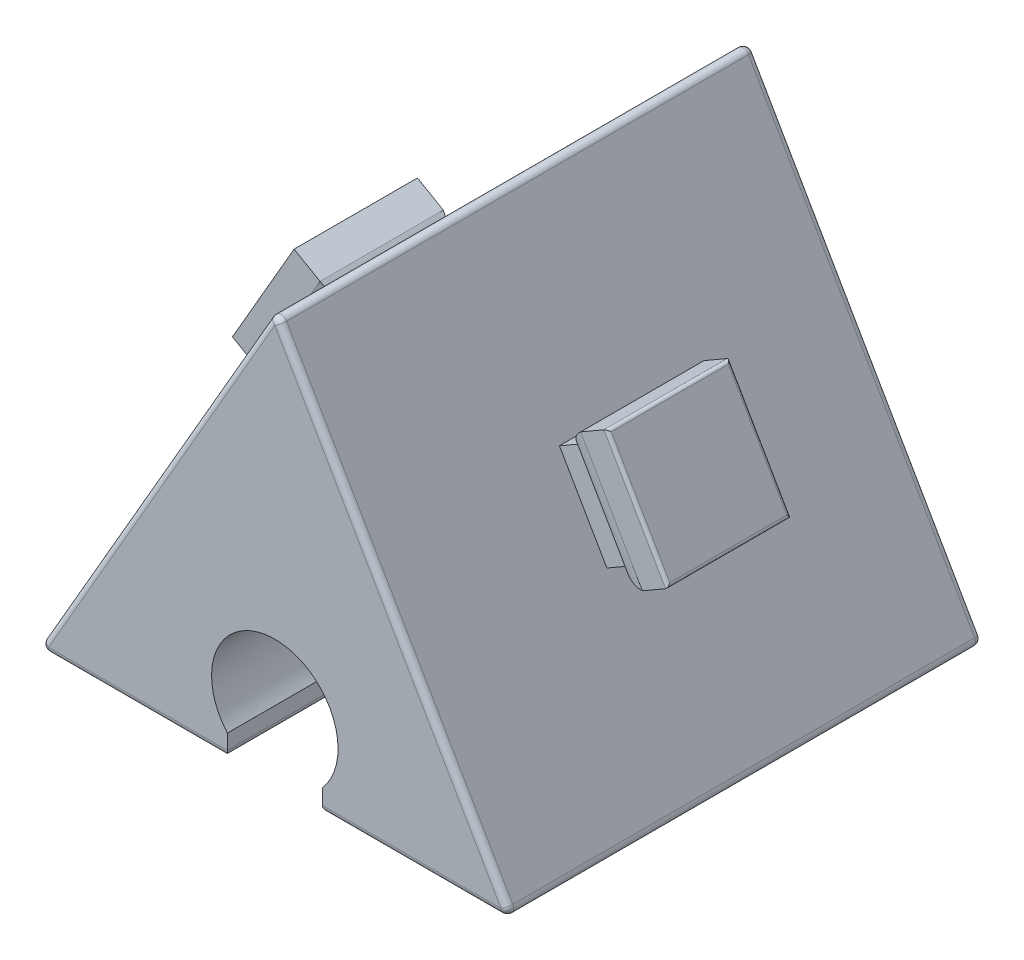
SolidWorks part; units mm, degrees
ref_plane "前视基准面" through (0, 0, 0) normal (0, 0, 1) x (1, 0, 0)
ref_plane "上视基准面" through (0, 0, 0) normal (0, 1, 0) x (1, 0, 0)
ref_plane "右视基准面" through (0, 0, 0) normal (1, 0, 0) x (0, 0, -1)
sketch "草图1" plane through (0, 0, 0) normal (0, 0, 1) x (1, 0, 0)
  line L0 (-7.5, 0) -> (0, 12.9904)
  line L1 (7.5, 0) -> (0, 12.9904)
  line L2 (-7.5, 0) -> (7.5, 0)
extrude "凸台-拉伸1" add sketch "草图1" along normal blind 7.5 and the other way blind 7.5
sketch "草图2" plane through (0, 0, 7.5) normal (0, 0, 1) x (1, 0, 0)
  line L0 (-1.5, 0.6771) -> (-1.5, 0)
  line L1 (-7.5, 0) -> (7.5, 0) construction
  line L3 (1.5, 0.6771) -> (1.5, 0)
  line L4 (1.5, 0) -> (-1.5, 0)
  arc A0 (1.5, 0.6771) -> (-1.5, 0.6771) centre (0, 2) ccw
extrude "切除-拉伸1" cut sketch "草图2" against normal up to next
sketch "草图3" plane through (0, 0, 0) normal (0, 0, 1) x (1, 0, 0)
  line L0 (3.5864, 8.1328) -> (5.0864, 5.5347)
  line L1 (5.9151, 7.7452) -> (6.8901, 6.0564)
  line L2 (0, -1) -> (0, 14) construction
  line L3 (0, -7.1447) -> (0, 7.1447) construction
  line L4 (-4.9401, 9.4339) -> (-4.1222, 8.9617)
  line L5 (-5.9151, 7.7452) -> (-4.9401, 9.4339)
  line L6 (-6.8901, 6.0564) -> (-6.0722, 5.5842)
  line L7 (6.8901, 6.0564) -> (6.0722, 5.5842)
  line L8 (5.9151, 7.7452) -> (4.9401, 9.4339)
  line L9 (4.9401, 9.4339) -> (4.1222, 8.9617)
  line L10 (-5.9151, 7.7452) -> (-6.8901, 6.0564)
  line L11 (-3.5864, 8.1328) -> (-5.0864, 5.5347)
  arc A0 (4.1222, 8.9617) -> (3.5864, 8.1328) centre (5.4821, 7.4952) ccw
  arc A1 (5.0864, 5.5347) -> (6.0722, 5.5842) centre (5.4821, 7.4952) ccw
  arc A2 (-5.0864, 5.5347) -> (-6.0722, 5.5842) centre (-5.4821, 7.4952) cw
  arc A3 (-4.1222, 8.9617) -> (-3.5864, 8.1328) centre (-5.4821, 7.4952) cw
extrude "凸台-拉伸2" add sketch "草图3" along normal blind 2 and the other way blind 2
sketch "草图5" plane through (0, 0, 0) normal (0, 0, 1) x (1, 0, 0)
  line L0 (3.5864, 8.1328) -> (5.0864, 5.5347)
  line L1 (5.0864, 5.5347) -> (4.5, 5.1962)
  line L2 (7.5, 0) -> (0, 12.9904) construction
  line L3 (4.5, 5.1962) -> (3, 7.7942)
  line L4 (3, 7.7942) -> (3.5864, 8.1328)
extrude "凸台-拉伸4" add sketch "草图5" along normal blind 1.5 and the other way blind 1.5
sketch "草图6" plane through (-0.9, 1.5588, 0) normal (0.5, -0.866, 0) x (0.866, 0.5, 0)
  line L0 (6.9565, 0) -> (9.3473, 0) construction
  line L2 (8.9952, -2) -> (8.9952, -1.95)
  line L3 (8.9952, 1.95) -> (8.0508, 1.95)
  line L4 (7.1723, 1.5) -> (7.1723, 2)
  line L5 (7.1723, 2) -> (8.9952, 2)
  line L6 (8.9952, 2) -> (8.9952, 1.95)
  line L7 (7.1723, -2) -> (8.9952, -2)
  line L8 (7.1723, -1.5) -> (7.1723, -2)
  line L9 (8.9952, -1.95) -> (8.0508, -1.95)
  arc A0 (8.0508, -1.95) -> (7.1723, -1.5) centre (8.4952, 0) cw
  arc A1 (8.0508, 1.95) -> (7.1723, 1.5) centre (8.4952, 0) ccw
extrude "切除-拉伸2" cut sketch "草图6" against normal through all
fillet "圆角1" radius 0.1 4 edges at (6.8901, 6.0564, 0) (5.9151, 7.7452, 1.95) (4.9401, 9.4339, 0) (5.9151, 7.7452, -1.95)
fillet "圆角2" radius 0.2 13 edges at (4.5, 0, 7.5) (7.5, 0, 0) (4.5, 0, -7.5) (1.5, 0, 0) (-4.5, 0, -7.5) (-7.5, 0, 0) (-4.5, 0, 7.5) (-1.5, 0, 0) (-3.75, 6.4952, -7.5) (3.75, 6.4952, -7.5) (-3.75, 6.4952, 7.5) (0, 12.9904, 0) (3.75, 6.4952, 7.5)
mirror "镜向9" about plane through (0, 0, 0) normal (1, 0, 0) of "凸台-拉伸4"
sketch "草图7" plane through (0.9, 1.5588, 0) normal (-0.5, -0.866, 0) x (0.866, -0.5, 0)
  line L4 (-8.9952, 2) -> (-7.1723, 2)
  line L5 (-8.9952, 2) -> (-8.9952, 1.95)
  line L6 (-8.9952, -2) -> (-7.1723, -2)
  line L7 (-7.1723, 2) -> (-7.1723, 1.5)
  line L8 (-7.1723, -1.5) -> (-7.1723, -2)
  line L10 (-8.9952, 1.95) -> (-8.0508, 1.95)
  line L11 (-8.9952, -1.95) -> (-8.9952, -2)
  line L13 (-8.9952, -1.95) -> (-8.0508, -1.95)
  arc A0 (-8.0508, -1.95) -> (-7.1723, -1.5) centre (-8.4952, 0) ccw
  arc A1 (-7.1723, 1.5) -> (-8.0508, 1.95) centre (-8.4952, 0) ccw
extrude "切除-拉伸3" cut sketch "草图7" against normal up to surface (3.9 mm away) up to face at (-4.5311, 9.1978, 0)
